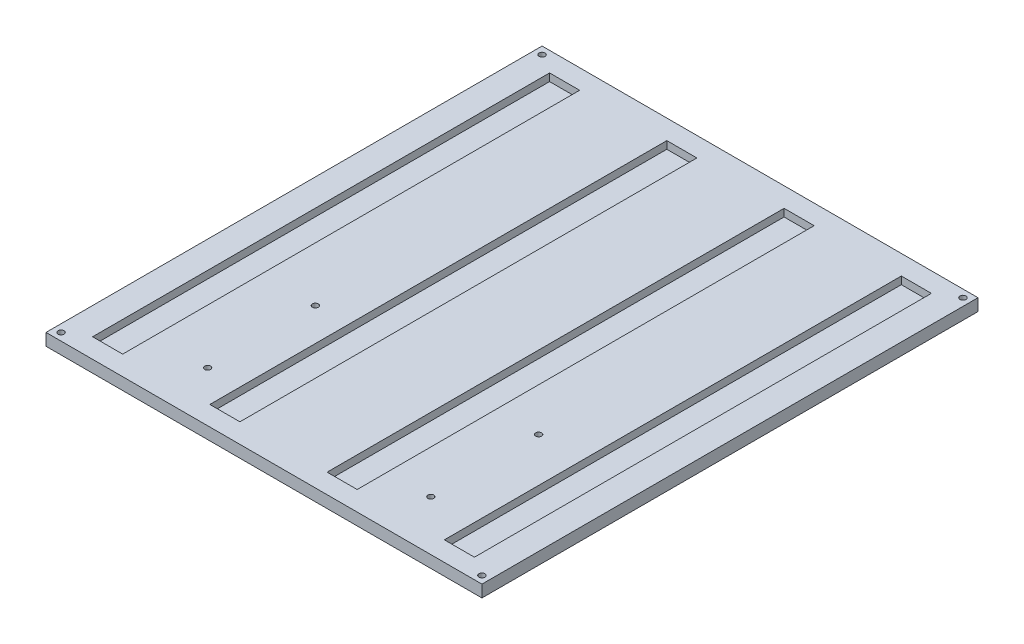
SolidWorks part; units mm, degrees
ref_plane "Front Plane" through (0, 0, 0) normal (0, 0, 1) x (1, 0, 0)
ref_plane "Top Plane" through (0, 0, 0) normal (0, 1, 0) x (1, 0, 0)
ref_plane "Right Plane" through (0, 0, 0) normal (1, 0, 0) x (0, 0, -1)
sketch "Sketch2" plane through (0, 0, 0) normal (0, 1, 0) x (1, 0, 0)
  line L0 (-24.5, -76) -> (-24.5, 76)
  line L1 (-72.5, -82.5) -> (72.5, -82.5)
  line L2 (-72.5, -82.5) -> (-72.5, 82.5)
  line L3 (-72.5, 82.5) -> (72.5, 82.5)
  line L4 (72.5, -82.5) -> (72.5, 82.5)
  line L5 (-63.5, -76) -> (-53.5, -76)
  line L6 (-63.5, -76) -> (-63.5, 76)
  line L7 (-63.5, 76) -> (-53.5, 76)
  line L8 (-53.5, -76) -> (-53.5, 76)
  line L9 (-63.5, -76) -> (-53.5, 76) construction
  line L10 (-63.5, 76) -> (-53.5, -76) construction
  line L11 (-24.5, -76) -> (-14.5, -76)
  line L12 (-14.5, -76) -> (-14.5, 76)
  line L13 (-24.5, 76) -> (-14.5, 76)
  line L14 (14.5, -76) -> (14.5, 76)
  line L15 (14.5, -76) -> (24.5, -76)
  line L16 (24.5, -76) -> (24.5, 76)
  line L17 (14.5, 76) -> (24.5, 76)
  line L18 (53.5, -76) -> (53.5, 76)
  line L19 (53.5, -76) -> (63.5, -76)
  line L20 (63.5, -76) -> (63.5, 76)
  line L21 (53.5, 76) -> (63.5, 76)
  point P0 (0, 0)
  point P6 (0, 82.5)
  point P7 (-72.5, 0)
  point P8 (-58.5, 0)
  dimension "D1" = 145
  dimension "D2" = 165
  dimension "D3" = 10
  dimension "D4" = 152
  dimension "D5" = 58.5
  dimension "D6" = 4
  dimension "D7" = 29
extrude "Boss-Extrude1" add sketch "Sketch2" against normal blind 4 contours L2 L1 L4 L3
extrude "Cut-Extrude1" cut sketch "Sketch2<3>" against normal blind 2.5 contours L6 L5 L8 L7 | L0 L13 L12 L11 | L14 L17 L16 L15 | L18 L21 L20 L19
sketch "Sketch2<3>" plane through (0, 0, 0) normal (0, 1, 0) x (1, 0, 0) same geometry as "Sketch2"
sketch "Sketch3" plane through (0, -4, 0) normal (0, -1, 0) x (1, 0, 0)
  line L0 (-70, -80) -> (70, 80)
  line L1 (-70, 80) -> (70, 80) construction
  line L2 (-70, 80) -> (-70, -80) construction
  line L3 (-70, -80) -> (70, -80) construction
  line L4 (70, 80) -> (70, -80) construction
  circle A0 centre (-70, 80) radius 1
  circle A1 centre (-70, 80) radius 1.25
  circle A2 centre (70, 80) radius 1.25
  circle A3 centre (70, 80) radius 1
  circle A4 centre (70, -80) radius 1.25
  circle A5 centre (70, -80) radius 1
  circle A6 centre (-70, -80) radius 1.25
  circle A7 centre (-70, -80) radius 1
  point P11 (0, 0)
  dimension "D1" = 2
  dimension "D2" = 2.5
  dimension "D5" = 2.5
  dimension "D6" = 2
  dimension "D7" = 2
  dimension "D8" = 2.5
  dimension "D9" = 2.5
  dimension "D10" = 2
  dimension "D3" = 160
  dimension "D4" = 140
extrude "Cut-Extrude3" cut sketch "Sketch3" against normal blind 5 contours A5 | A7 | A0 | A3
sketch "Sketch5" plane through (0, -4, 0) normal (0, 1, 0) x (1, 0, 0)
  line L1 (-35.4387, -29.9718) -> (38.8313, -29.9718) construction
  line L2 (-35.4387, -29.9718) -> (-35.4387, -65.8118) construction
  line L3 (-35.4387, -65.8118) -> (38.8313, -65.8118) construction
  line L4 (38.8313, -29.9718) -> (38.8313, -65.8118) construction
  circle A0 centre (-35.4387, -29.9718) radius 0.98
  circle A1 centre (38.8313, -29.9718) radius 0.98
  circle A2 centre (38.8313, -65.8118) radius 0.98
  circle A3 centre (-35.4387, -65.8118) radius 0.98
  dimension "D3" = 1.96
  dimension "D1" = 74.27
  dimension "D2" = 35.84
extrude "Cut-Extrude4" cut sketch "Sketch5" along normal blind 4 contours A0 | A1 | A2 | A3
